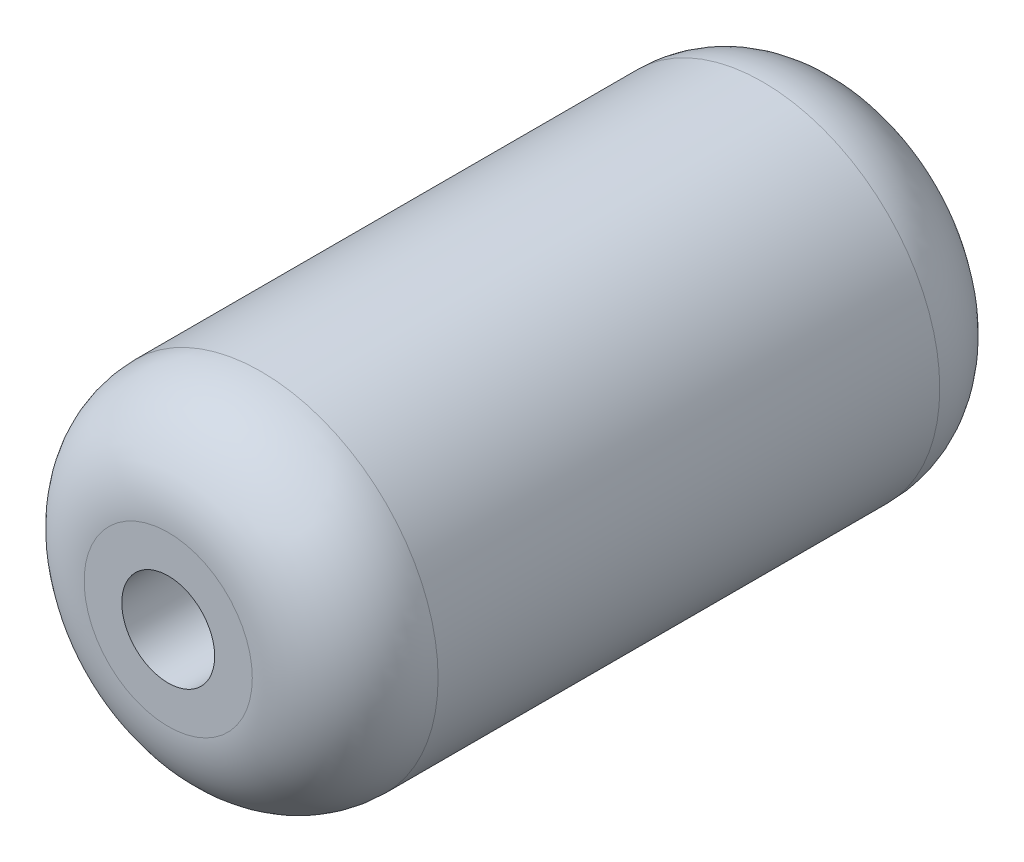
SolidWorks part; units mm, degrees
ref_plane "Alzado" through (0, 0, 0) normal (0, 0, 1) x (1, 0, 0)
ref_plane "Planta" through (0, 0, 0) normal (0, 1, 0) x (1, 0, 0)
ref_plane "Vista lateral" through (0, 0, 0) normal (1, 0, 0) x (0, 0, -1)
sketch "Croquis1" plane through (0, 0, 0) normal (0, 0, 1) x (1, 0, 0)
  circle A0 centre (0, 0) radius 19.05
  circle A1 centre (0, 0) radius 5
  dimension "D1" = 38.1
  dimension "D2" = 10
extrude "Saliente-Extruir1" add sketch "Croquis1" along normal blind 74
fillet "Redondeo1" radius 10 2 edges at (19.05, 0, 74) (19.05, 0, 0)
